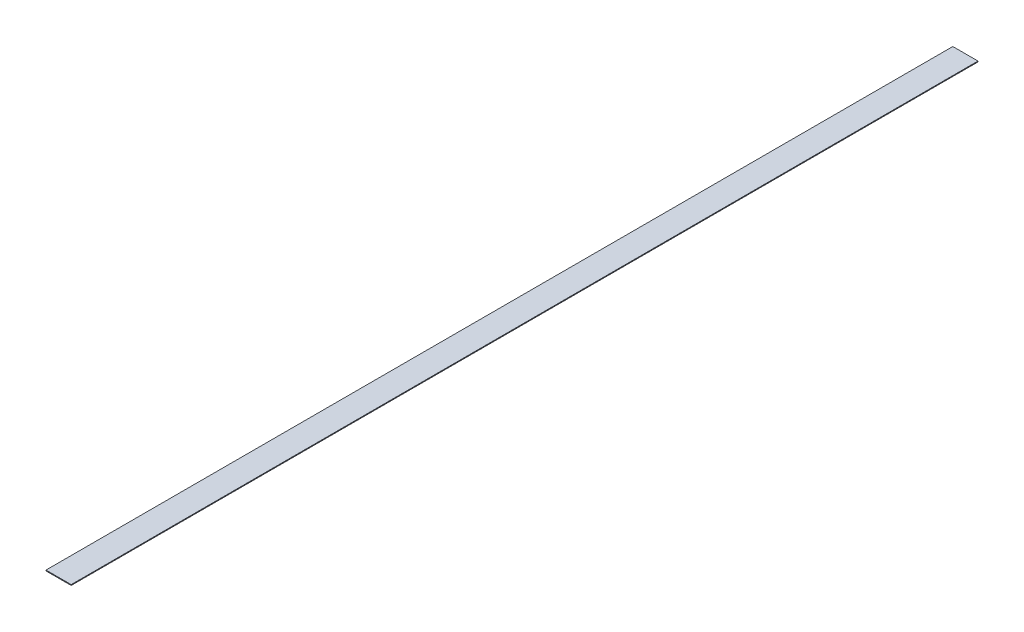
SolidWorks part; units mm, degrees
material "NEOPRENE"
ref_plane "Front Plane" through (0, 0, 0) normal (0, 0, 1) x (1, 0, 0)
ref_plane "Top Plane" through (0, 0, 0) normal (0, 1, 0) x (1, 0, 0)
ref_plane "Right Plane" through (0, 0, 0) normal (1, 0, 0) x (0, 0, -1)
sketch "Sketch1" plane through (0, 0, 0) normal (0, 0, 1) x (1, 0, 0)
  line L0 (0, 0.3969) -> (0, -0.3969)
  line L1 (-12.7, 0) -> (12.7, 0) construction
  point P6 (0, 0)
  dimension "Width" = 25.4
  dimension "Thk" = 0.7937
sketch "Sketch2" plane through (0, 0, 0) normal (1, 0, 0) x (0, 0, -1)
  line L0 (457.2, 0) -> (-457.2, 0)
  point P4 (0, 0)
  dimension "Length" = 914.4
sketch "Sketch3" plane through (0, 0, 0) normal (0, 0, 1) x (1, 0, 0)
  line L1 (12.7, 0.3969) -> (-12.7, 0.3969)
  line L2 (12.7, 0.3969) -> (12.7, -0.3969)
  line L3 (12.7, -0.3969) -> (-12.7, -0.3969)
  line L4 (-12.7, 0.3969) -> (-12.7, -0.3969)
  line L5 (12.7, 0.3969) -> (-12.7, -0.3969) construction
  line L6 (12.7, -0.3969) -> (-12.7, 0.3969) construction
  point P0 (0, 0)
extrude "Boss-Extrude1" add sketch "Sketch3" along normal up to vertex (457.2 mm away) and the other way up to vertex (457.2 mm away) up to point (0, 0, 457.2) other way up to point (0, 0, -457.2)
sketch "Sketch4" plane through (0, 0.3969, 0) normal (0, 1, 0) x (1, 0, 0)
  line L5 (7.5828, -11.6745) -> (-7.5828, -11.6745)
  line L6 (7.5828, -11.6745) -> (7.5828, 11.6745)
  line L7 (7.5828, 11.6745) -> (-7.5828, 11.6745)
  line L8 (-7.5828, -11.6745) -> (-7.5828, 11.6745)
  line L9 (7.5828, -11.6745) -> (-7.5828, 11.6745) construction
  line L10 (7.5828, 11.6745) -> (-7.5828, -11.6745) construction
  line L11 (12.7, -457.2) -> (-12.7, -457.2)
  line L12 (12.7, -457.2) -> (12.7, 457.2)
  line L13 (12.7, 457.2) -> (-12.7, 457.2)
  line L14 (-12.7, -457.2) -> (-12.7, 457.2)
  line L15 (12.7, -457.2) -> (-12.7, 457.2) construction
  line L16 (12.7, 457.2) -> (-12.7, -457.2) construction
  point P0 (0, 0)
  point P5 (0, 0)
  dimension "D3" = 23.3489
  dimension "D4" = 15.1657
extrude "Cut-Extrude1" [suppressed] cut sketch "Sketch4" against normal through all
